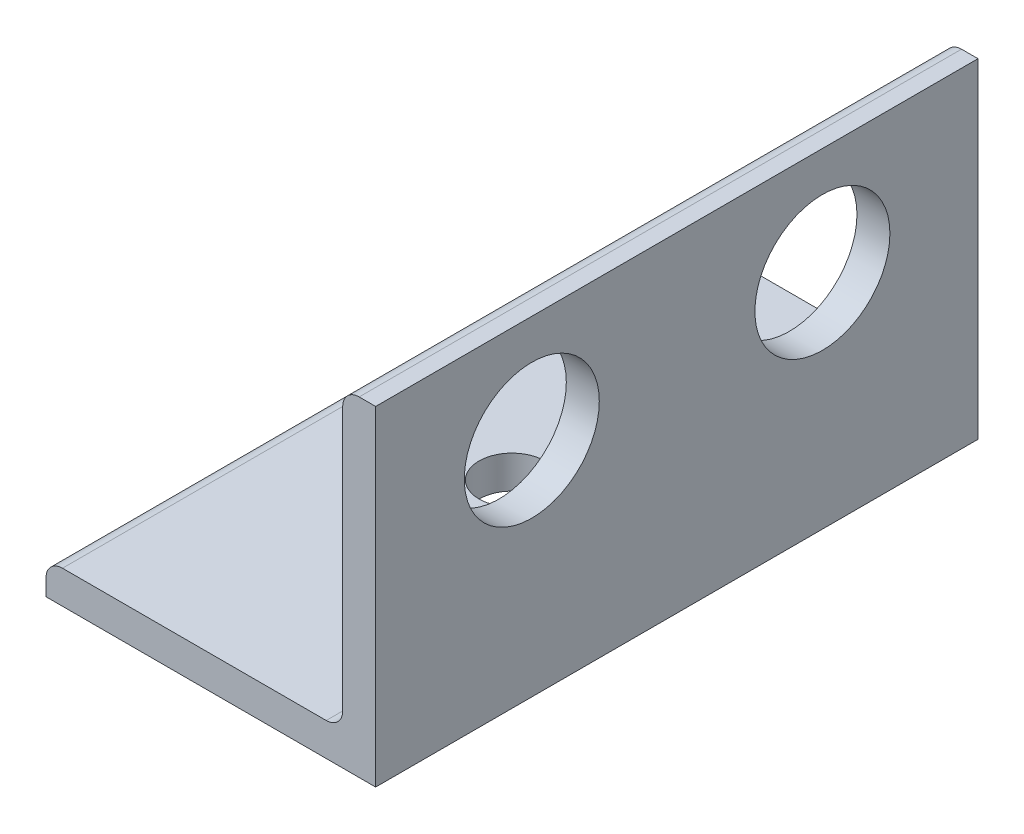
SolidWorks part; units mm, degrees
material "McMaster 6061-T6"
ref_plane "Front Plane" through (0, 0, 0) normal (0, 0, 1) x (1, 0, 0)
ref_plane "Top Plane" through (0, 0, 0) normal (0, 1, 0) x (1, 0, 0)
ref_plane "Right Plane" through (0, 0, 0) normal (1, 0, 0) x (0, 0, -1)
sketch "Sketch2" plane through (0, 0, 0) normal (0, 0, 1) x (1, 0, 0)
  line L0 (-7.9375, 0) -> (7.9375, 0)
  line L1 (7.9375, 0) -> (7.9375, 15.875)
  line L2 (7.9375, 15.875) -> (6.35, 15.875) construction
  line L3 (6.35, 15.0813) -> (6.35, 2.3812)
  line L4 (5.5563, 1.5875) -> (-7.1438, 1.5875)
  line L5 (-7.9375, 0) -> (-7.9375, 1.5875) construction
  line L6 (7.1438, 15.875) -> (7.9375, 15.875)
  line L7 (-7.9375, 0.7937) -> (-7.9375, 0)
  arc A0 (6.35, 15.0813) -> (7.1438, 15.875) centre (7.1438, 15.0813) cw
  arc A1 (-7.9375, 0.7937) -> (-7.1438, 1.5875) centre (-7.1438, 0.7937) cw
  arc A2 (6.35, 2.3812) -> (5.5563, 1.5875) centre (5.5563, 2.3812) cw
  dimension "Vert" = 15.875
  dimension "Horz" = 15.875
  dimension "Thickness" = 1.5875
extrude "Boss-Extrude1" add sketch "Sketch2" along normal mid plane 304.8
ref_plane "Contact Plane 1" through (0, 1.5875, 0) normal (0, 1, 0) x (1, 0, 0)
ref_plane "Contact Plane 2" through (6.35, 0, 0) normal (-1, 0, 0) x (0, 0, 1)
sketch "Sketch3" plane through (7.9375, 0, 0) normal (1, 0, 0) x (0, 0, -1)
  line L2 (152.4, 0) -> (152.4, 15.875) construction
  arc A0 (141.6558, 10.7061) -> (148.1582, 10.7061) centre (144.907, 10.7061) ccw construction
  arc A1 (141.6558, 10.7061) -> (148.1582, 10.7061) centre (144.907, 10.7061) ccw construction
  arc A2 (127.6604, 10.7061) -> (134.1628, 10.7061) centre (130.9116, 10.7061) ccw construction
  arc A3 (127.6604, 10.7061) -> (134.1628, 10.7061) centre (130.9116, 10.7061) ccw construction
  circle A4 centre (144.907, 10.7061) radius 3.2512
  circle A5 centre (130.9116, 10.7061) radius 3.2512
  point P4 (152.4, 7.9375)
extrude "Cut-Extrude1" cut sketch "Sketch3" against normal up to next contours A4 | A5 region at (7.9375, 10.7061, -144.907) region at (7.9375, 10.7061, -130.9116)
sketch "Sketch4" plane through (0, 0, 152.4) normal (0, 0, 1) x (1, 0, 0)
  line L6 (-7.9375, 0.7937) -> (-7.9375, 0)
  line L7 (-7.9375, 0) -> (7.9375, 0)
  line L8 (7.9375, 0) -> (7.9375, 15.875)
  line L9 (7.9375, 15.875) -> (7.1438, 15.875)
  line L10 (6.35, 15.0813) -> (6.35, 2.3812)
  line L11 (5.5563, 1.5875) -> (-7.1438, 1.5875)
  line L12 (-7.9375, 0.7937) -> (-7.9375, 0)
  line L13 (-7.9375, 0) -> (7.9375, 0)
  line L14 (7.9375, 0) -> (7.9375, 15.875)
  line L15 (7.9375, 15.875) -> (7.1438, 15.875)
  line L16 (6.35, 15.0813) -> (6.35, 2.3812)
  line L17 (5.5563, 1.5875) -> (-7.1438, 1.5875)
  arc A3 (7.1438, 15.875) -> (6.35, 15.0813) centre (7.1438, 15.0813) ccw
  arc A4 (5.5563, 1.5875) -> (6.35, 2.3812) centre (5.5563, 2.3812) ccw
  arc A5 (-7.1438, 1.5875) -> (-7.9375, 0.7937) centre (-7.1438, 0.7937) ccw
  arc A6 (7.1438, 15.875) -> (6.35, 15.0813) centre (7.1438, 15.0813) ccw
  arc A7 (5.5563, 1.5875) -> (6.35, 2.3812) centre (5.5563, 2.3812) ccw
  arc A8 (-7.1438, 1.5875) -> (-7.9375, 0.7937) centre (-7.1438, 0.7937) ccw
  dimension "D1" = 0
extrude "Cut-Extrude2" cut sketch "Sketch4" against normal up to surface (275.7932 mm away)
sketch "Sketch5" plane through (0, 0, 0) normal (0, -1, 0) x (1, 0, 0)
  line L0 (7.9375, -152.4) -> (-7.9375, -123.3932) construction
  line L4 (7.9375, -123.3932) -> (-7.9375, -123.3932)
  line L5 (-7.9375, -123.3932) -> (-7.9375, -152.4)
  line L6 (-7.9375, -152.4) -> (7.9375, -152.4)
  line L7 (7.9375, -152.4) -> (7.9375, -123.3932)
  line L8 (7.9375, -123.3932) -> (-7.9375, -123.3932) construction
  line L9 (-7.9375, -123.3932) -> (-7.9375, -152.4) construction
  line L10 (-7.9375, -152.4) -> (7.9375, -152.4) construction
  line L11 (7.9375, -152.4) -> (7.9375, -123.3932) construction
  circle A0 centre (0, -137.8966) radius 1.5875
  dimension "D2" = 3.175
  dimension "D1" = 0
extrude "Cut-Extrude3" cut sketch "Sketch5" against normal up to next
